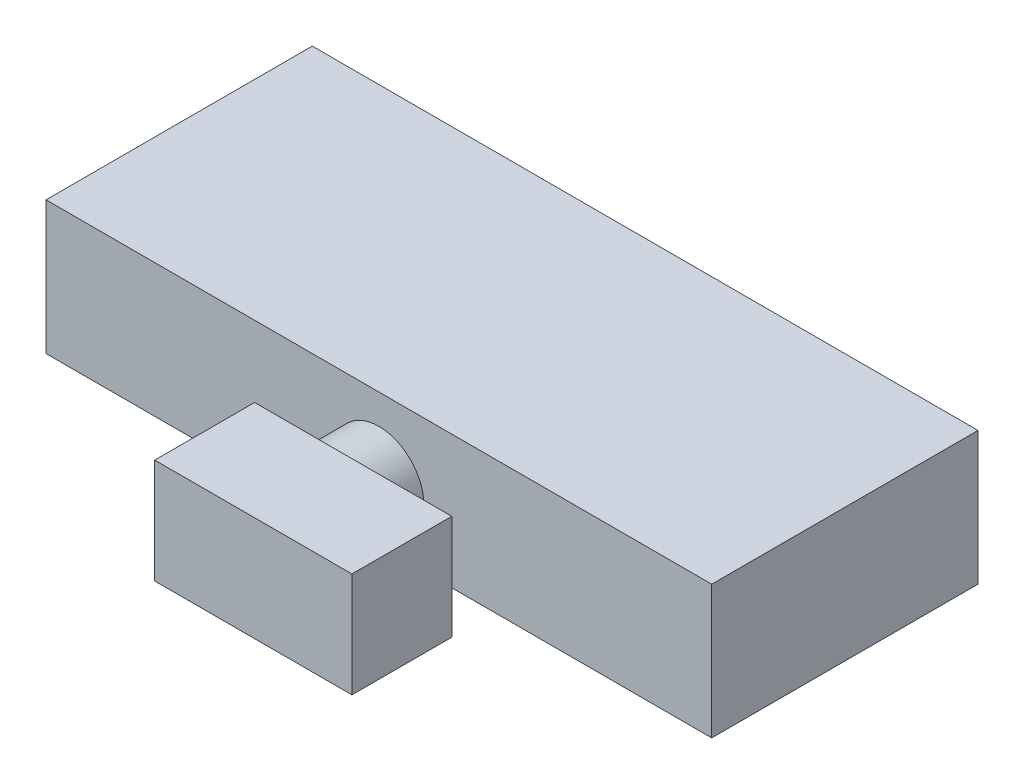
SolidWorks part; units mm, degrees
ref_plane "Front Plane" through (0, 0, 0) normal (0, 0, 1) x (1, 0, 0)
ref_plane "Top Plane" through (0, 0, 0) normal (0, 1, 0) x (1, 0, 0)
ref_plane "Right Plane" through (0, 0, 0) normal (1, 0, 0) x (0, 0, -1)
sketch "Sketch2" plane through (0, 0, 0) normal (0, 0, 1) x (1, 0, 0)
  line L1 (-47.8692, 21.2481) -> (206.1308, 21.2481)
  line L2 (-47.8692, 21.2481) -> (-47.8692, -80.3519)
  line L3 (-47.8692, -80.3519) -> (206.1308, -80.3519)
  line L4 (206.1308, 21.2481) -> (206.1308, -80.3519)
  dimension "D1" = 101.6
  dimension "D2" = 254
extrude "Boss-Extrude1" add sketch "Sketch2" along normal blind 50.8
sketch "Sketch3" plane through (0, 21.2481, 0) normal (0, 1, 0) x (1, 0, 0)
  circle A0 centre (79.1308, -28.4831) radius 17.1408
extrude "Boss-Extrude2" add sketch "Sketch3" along normal blind 19.05
sketch "Sketch4" plane through (0, 40.2981, 0) normal (0, 1, 0) x (1, 0, 0)
  line L1 (50.7675, -8.111) -> (126.0034, -8.111)
  line L2 (50.7675, -8.111) -> (50.7675, -48.0661)
  line L3 (50.7675, -48.0661) -> (126.0034, -48.0661)
  line L4 (126.0034, -8.111) -> (126.0034, -48.0661)
extrude "Boss-Extrude3" add sketch "Sketch4" along normal blind 38.1
scale "Scale2" scale about centroid uniform scaling yes scale factor 0.06
move or copy body "rotate" bodies to move or copy 105 copy no rotation origin (0, 33.6669, 26.5501) rotation axis (1, 0, 0) rotation angle 90
scale "Scale5" scale about centroid uniform scaling yes scale factor 0.25
move or copy body "-4 x" bodies to move or copy 111 copy no translate (-101.6, 0, 0)
move or copy body "-2 y" bodies to move or copy 117 copy no translate (0, -50.8, 0)
scale "Scale6" bodies to scale 121 scale about centroid uniform scaling yes scale factor 0.25
move or copy body "-2.1z" bodies to move or copy 122 copy no translate (0, 0, -53.34)
